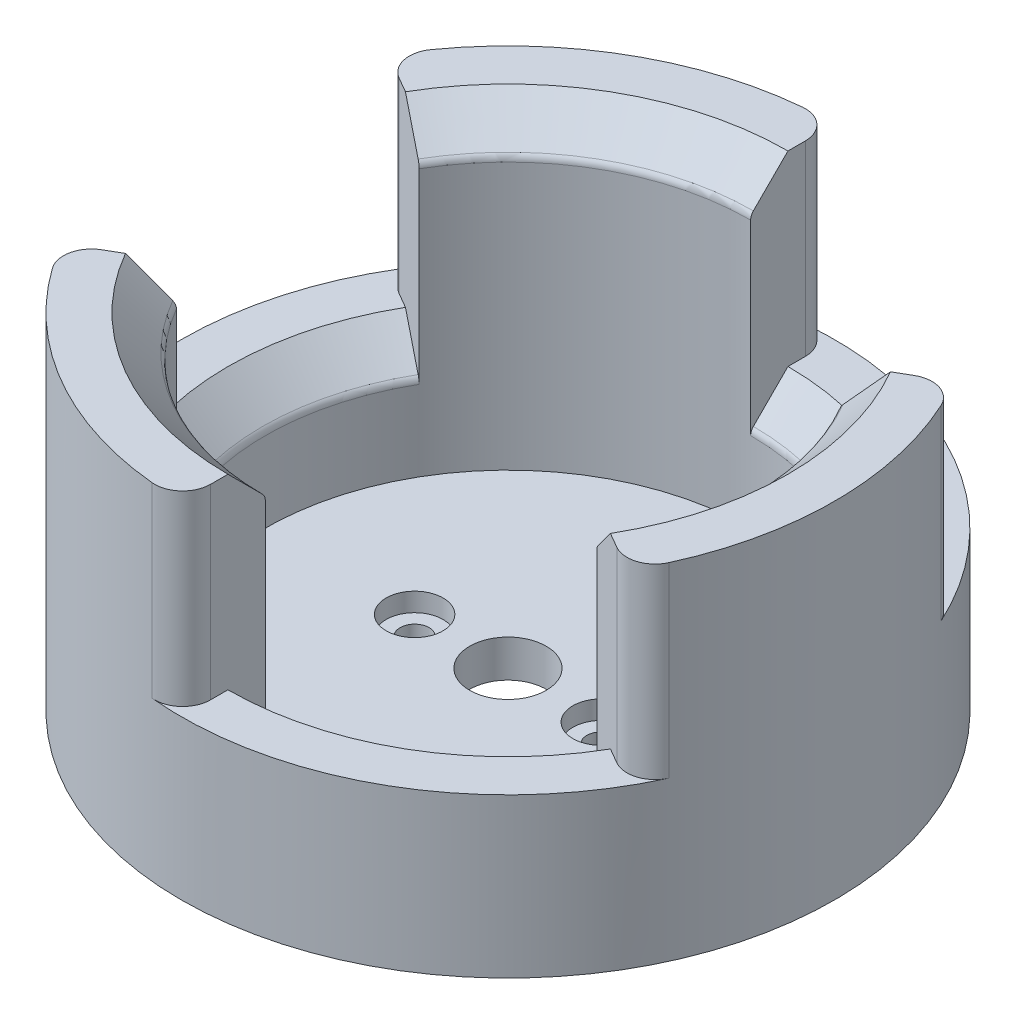
SolidWorks part; units mm, degrees
ref_plane "前视基准面" through (0, 0, 0) normal (0, 0, 1) x (1, 0, 0)
ref_plane "上视基准面" through (0, 0, 0) normal (0, 1, 0) x (1, 0, 0)
ref_plane "右视基准面" through (0, 0, 0) normal (1, 0, 0) x (0, 0, -1)
other "Configuration Table"
sketch "草图1" plane through (0, 0, 0) normal (0, 1, 0) x (1, 0, 0)
  circle A0 centre (0, 0) radius 26
  circle A1 centre (0, 0) radius 35
  dimension "D1" = 52
  dimension "D2" = 70
extrude "凸台-拉伸1" add sketch "草图1" along normal blind 33
extrude "凸台-拉伸2" add sketch "草图1<5>" against normal blind 4 contours A0 | A1 A0 region at (0, 0, 0) region at (-34.0101, 0, 0)
sketch "草图1<5>" plane through (0, 0, 0) normal (0, 1, 0) x (1, 0, 0) same geometry as "草图1"
chamfer "倒角1" distance 4 angle 45 1 edges at (0, 33, 26)
fillet "圆角1" radius 1 1 edges at (0, 29, 26)
sketch "草图3" plane through (0, 0, 0) normal (0, 1, 0) x (1, 0, 0)
  line L0 (0, 0) -> (10, 0)
  line L1 (0, 0) -> (0, -5.0818)
  circle A1 centre (10, 0) radius 3.05
  circle A2 centre (-10, 0) radius 3.05
  dimension "D1" = 6.1
  dimension "D2" = 10
extrude "切除-拉伸1" cut sketch "草图3" against normal blind 2 contours A2 | A1 region at (10, 0, 2.9637) region at (-10, 0, 0)
sketch "草图4" plane through (0, -2, 0) normal (0, 1, 0) x (1, 0, 0)
  circle A0 centre (-10, 0) radius 1.55
  circle A1 centre (10, 0) radius 1.55
  dimension "D1" = 3.1
extrude "切除-拉伸3" cut sketch "草图4" against normal blind 7.5
sketch "草图6" plane through (0, 0, 0) normal (0, 1, 0) x (1, 0, 0)
  circle A0 centre (0, 0) radius 4.1
  dimension "D1" = 8.2
extrude "切除-拉伸4" cut sketch "草图6" against normal blind 5
sketch "草图7" plane through (0, 0, 0) normal (0, 1, 0) x (1, 0, 0)
  line L0 (0, 0) -> (0, -35)
  line L1 (0, 0) -> (30.3109, -17.5)
  line L2 (0, 0) -> (47.8138, 0) construction
  circle A0 centre (0, 0) radius 35 construction
  arc A1 (0, -35) -> (30.3109, -17.5) centre (0, 0) ccw
  dimension "D1" = 30
  dimension "D2" = 60
extrude "切除-拉伸5" cut sketch "草图7" along normal through all from offset 13
pattern_circular "阵列(圆周)2" count 3 every 120 about axis through (0, 33, 0) along (0, -1, 0) of "切除-拉伸5"
chamfer "倒角2" distance 4 angle 45 3 edges at (13, 13, -22.5167) (13, 13, 22.5167) (-26, 13, 0)
fillet "圆角2" radius 1 3 edges at (13, 9, 22.5167) (13, 9, -22.5167) (-26, 9, 0)
fillet "圆角3" radius 3 6 edges at (-30.3109, 23, 17.5) (0, 23, 35) (30.3109, 23, 17.5) (30.3109, 23, -17.5) (-30.3109, 23, -17.5) (0, 23, -35)
